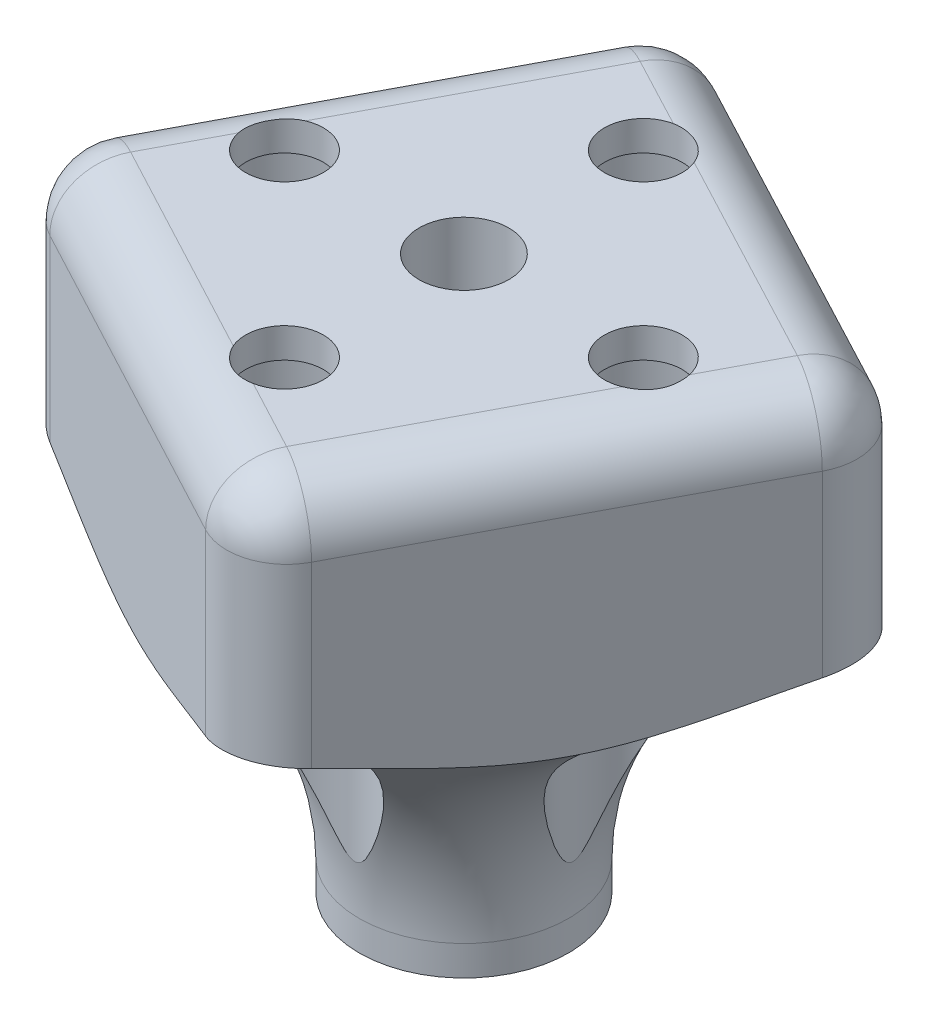
SolidWorks part; units mm, degrees
ref_plane "Alzado" through (0, 0, 0) normal (0, 0, 1) x (1, 0, 0)
ref_plane "Planta" through (0, 0, 0) normal (0, 1, 0) x (1, 0, 0)
ref_plane "Vista lateral" through (0, 0, 0) normal (1, 0, 0) x (0, 0, -1)
sketch "Croquis1" plane through (0, 0, 0) normal (0, 1, 0) x (1, 0, 0)
  circle A0 centre (0, 0) radius 3.5
  dimension "D1" = 7
extrude "Saliente-Extruir1" add sketch "Croquis1" along normal blind 10 and the other way blind 1
sketch "Croquis2" plane through (0, -1, 0) normal (0, -1, 0) x (1, 0, 0)
  line L0 (0, 2.9) -> (0, -2.9) construction
  line L1 (-2.2, -1.8894) -> (-2.2, 1.8894)
  line L2 (2.2, -1.8894) -> (2.2, 1.8894)
  arc A0 (-2.2, -1.8894) -> (2.2, -1.8894) centre (0, 0) ccw
  arc A1 (2.2, 1.8894) -> (-2.2, 1.8894) centre (0, 0) ccw
  dimension "D1" = 5.8
  dimension "D2" = 2.2
extrude "Cortar-Extruir2" cut sketch "Croquis2" against normal blind 8
sketch "Croquis4" plane through (0, 10, 0) normal (0, 1, 0) x (1, 0, 0)
  circle A0 centre (0, 0) radius 2
  dimension "D1" = 4
extrude "Cortar-Extruir4" cut sketch "Croquis4" against normal through all contours A0
ref_plane "Plano2" through (0, 10, 0) normal (0, 1, 0) x (1, 0, 0)
sketch "Croquis5" plane through (0, 10, 0) normal (0, 1, 0) x (1, 0, 0)
  circle A0 centre (0, 0) radius 12.5
  dimension "D1" = 25
extrude "Saliente-Extruir2" add sketch "Croquis5" along normal blind 7.5
sketch "Croquis6" plane through (0, 17.5, 0) normal (0, 1, 0) x (1, 0, 0)
  line L0 (0, 0) -> (-7.3361, 0) construction
  line L1 (0, 0) -> (0, -6) construction
  circle A0 centre (0, -6) radius 1.3
  circle A1 centre (-6, 0) radius 1.3
  circle A2 centre (0, 6) radius 1.3
  circle A3 centre (6, 0) radius 1.3
  point P14 (0, 0)
  dimension "D1" = 2.6
  dimension "D2" = 6
  dimension "D3" = 90
  dimension "D4" = 4
extrude "Cortar-Extruir5" cut sketch "Croquis6" against normal through all
sketch "Croquis7" plane through (0, 17.5, 0) normal (0, 1, 0) x (1, 0, 0)
  circle A0 centre (0, 0) radius 1.5
  dimension "D1" = 3
extrude "Cortar-Extruir6" cut sketch "Croquis7" against normal through all
sketch "Croquis8" plane through (0, 17.5, 0) normal (0, 1, 0) x (1, 0, 0)
  line L0 (3.447, -11.2534) -> (11.2229, 3.4631)
  line L1 (11.2229, 3.4631) -> (-3.4631, 11.2229)
  line L2 (-3.4631, 11.2229) -> (-11.2182, -3.4543)
  line L3 (-11.2182, -3.4543) -> (3.447, -11.2534)
  circle A0 centre (-6, 0) radius 1.3 construction
  circle A1 centre (0, 6) radius 1.3 construction
  circle A2 centre (0, 0) radius 13
  circle A3 centre (6, 0) radius 1.3 construction
  circle A4 centre (0, 0) radius 2 construction
  dimension "D3" = 5.5
  dimension "D4" = 3
  dimension "D5" = 3
  dimension "D6" = 3
  dimension "D7" = 11
  dimension "D1" = 16.6
  dimension "D2" = 16.61
extrude "Cortar-Extruir10" cut sketch "Croquis8" against normal through all
sketch "Croquis13" plane through (0, 10, 0) normal (0, -1, 0) x (-1, 0, 0)
  circle A0 centre (6, 0) radius 2.35
  circle A1 centre (0, -6) radius 2.35
  circle A2 centre (-6, 0) radius 2.35
  circle A3 centre (0, 6) radius 2.35
  point P12 (0, 0)
  dimension "D1" = 4.7
  dimension "D2" = 4
extrude "Cortar-Extruir13" cut sketch "Croquis13" against normal blind 6.5
fillet "Redondeo2" radius 10 1 edges at (0, 10, 3.5)
fillet "Redondeo3" radius 2 8 edges at (11.2229, 13.6724, -3.4631) (3.447, 13.6746, 11.2534) (-11.2182, 13.6718, 3.4543) (-3.4631, 13.6724, -11.2229) (-3.8856, 17.5, 7.3539) (7.3349, 17.5, 3.8951) (3.8799, 17.5, -7.343) (-7.3407, 17.5, -3.8843)
